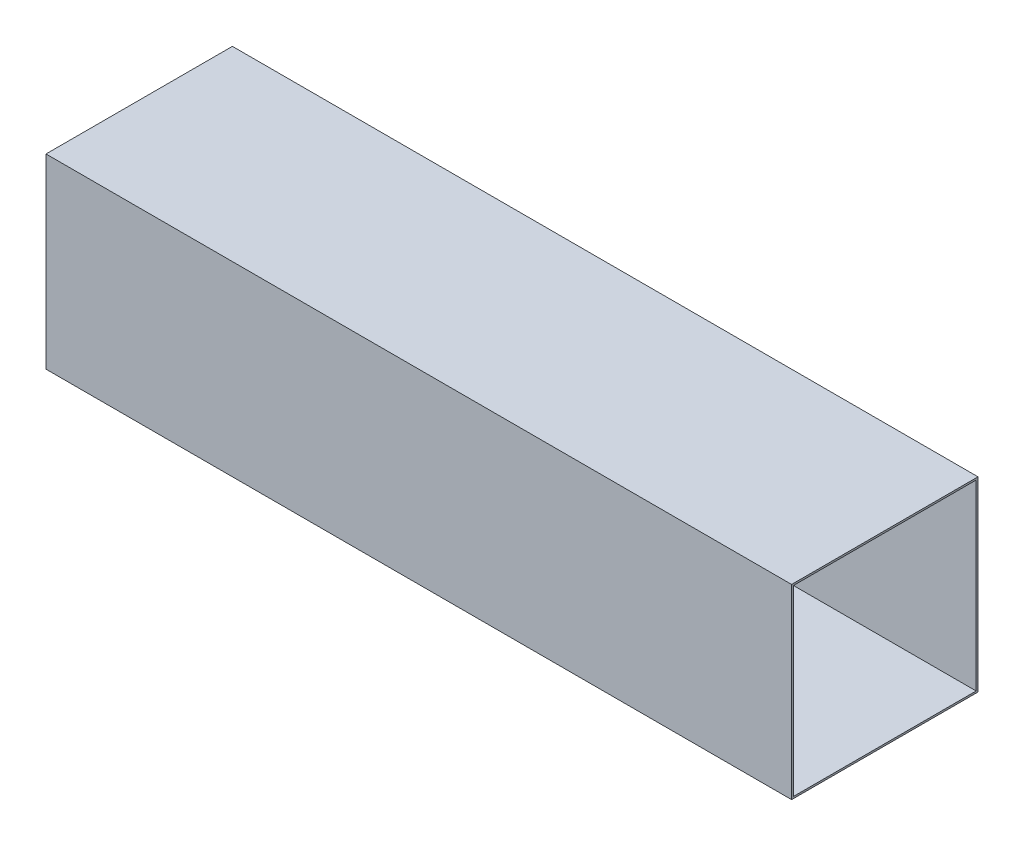
SolidWorks part; units mm, degrees
ref_plane "Ebene vorne" through (0, 0, 0) normal (0, 0, 1) x (1, 0, 0)
ref_plane "Ebene oben" through (0, 0, 0) normal (0, 1, 0) x (1, 0, 0)
ref_plane "Ebene rechts" through (0, 0, 0) normal (1, 0, 0) x (0, 0, -1)
sketch "Sketch1" plane through (0, 0, 0) normal (1, 0, 0) x (0, 0, -1)
  line L1 (0, 0) -> (100, 0)
  line L2 (0, 0) -> (0, 100)
  line L3 (0, 100) -> (100, 100)
  line L4 (100, 0) -> (100, 100)
  line L5 (1, 1) -> (99, 1)
  line L6 (1, 1) -> (1, 99)
  line L7 (1, 99) -> (99, 99)
  line L8 (99, 1) -> (99, 99)
  point P9 (0, 0.9651)
  point P10 (1, 1.4276)
  point P11 (15.9374, 1.1963)
  point P12 (16.9548, 14.6538)
  point P13 (15.8911, 1.2426)
  point P14 (17.371, 0)
  dimension "D1" = 1
  dimension "D2" = 1
  dimension "D3" = 1
  dimension "D4" = 1
  dimension "D5" = 100
  dimension "D6" = 100
extrude "Boss-Extrude1" add sketch "Sketch1" along normal blind 400
